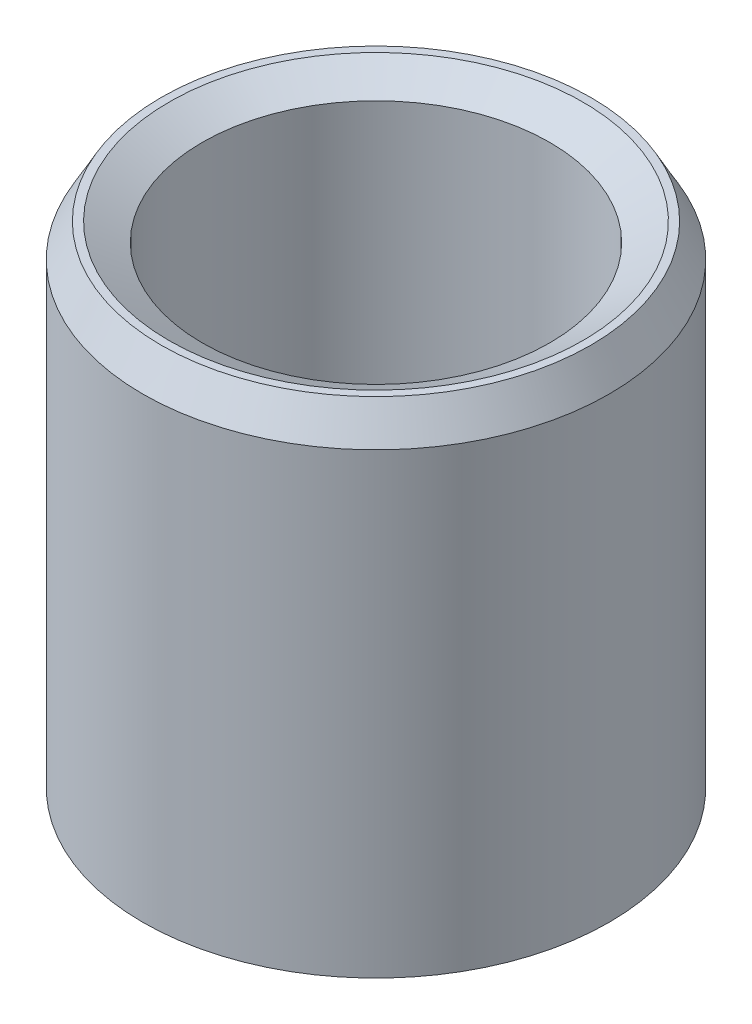
SolidWorks part; units mm, degrees
ref_plane "Front Plane" through (0, 0, 0) normal (0, 0, 1) x (1, 0, 0)
ref_plane "Top Plane" through (0, 0, 0) normal (0, 1, 0) x (1, 0, 0)
ref_plane "Right Plane" through (0, 0, 0) normal (1, 0, 0) x (0, 0, -1)
sketch "Sketch1" plane through (0, 0, 0) normal (0, 1, 0) x (1, 0, 0)
  circle A0 centre (0, 0) radius 22.5
  dimension "SLEEVE_OD" = 45
extrude "Boss-Extrude1" add sketch "Sketch1" along normal blind 49.116
sketch "Sketch2" plane through (0, 0, 0) normal (0, 1, 0) x (1, 0, 0)
  circle A0 centre (0, 0) radius 16.7642
  dimension "BORE_D" = 33.5284
extrude "Cut-Extrude1" cut sketch "Sketch2" along normal through all
chamfer "Chamfer1" distance 3.1888 angle 29.183 4 edges at (0, 49.116, 16.7642) (0, 0, 16.7642) (0, 0, 22.5) (0, 49.116, 22.5) first distance on face at (0, 49.116, 16.7642) first distance on face at (0, 0, 16.7642) first distance on face at (0, 49.116, 22.5)
